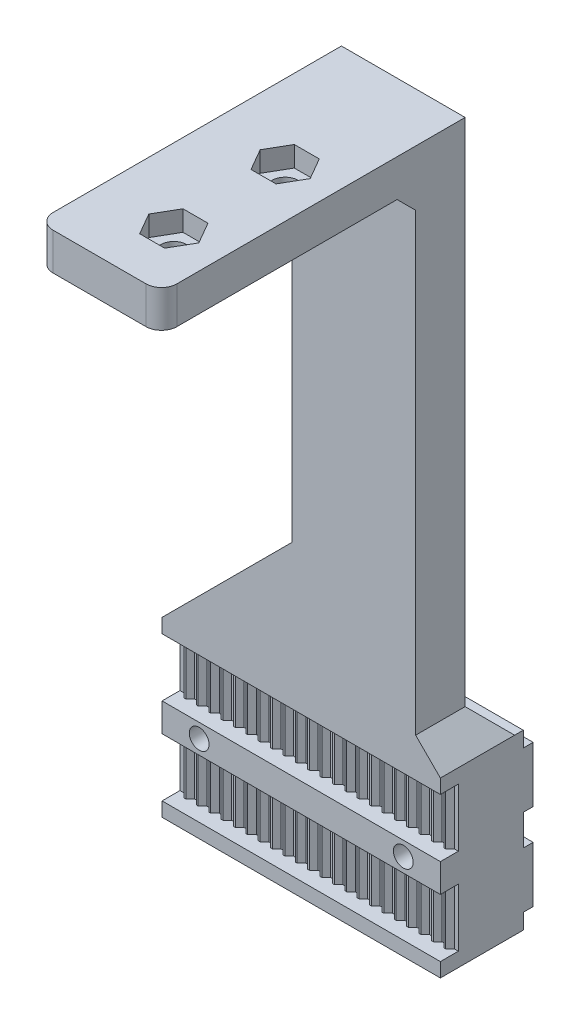
SolidWorks part; units mm, degrees
ref_plane "Спереди" through (0, 0, 0) normal (0, 0, 1) x (1, 0, 0)
ref_plane "Сверху" through (0, 0, 0) normal (0, 1, 0) x (1, 0, 0)
ref_plane "Справа" through (0, 0, 0) normal (1, 0, 0) x (0, 0, -1)
sketch "Эскиз1" plane through (0, 0, 0) normal (0, 0, 1) x (1, 0, 0)
  line L1 (0, -28) -> (-45, -28)
  line L2 (0, -28) -> (0, 0)
  line L3 (0, 0) -> (-45, 0)
  line L4 (-45, -28) -> (-45, 0)
  dimension "D1" = 28
  dimension "D2" = 45
extrude "Бобышка-Вытянуть1" add sketch "Эскиз1" along normal blind 13.4
sketch "Эскиз2" plane through (0, 0, 0) normal (0, 1, 0) x (1, 0, 0)
  line L6 (-45, 0) -> (-45, 1.6)
  line L90 (0, 0) -> (0, 1.6)
  line L91 (0, 0) -> (-45, 0)
  line L93 (-45, 1.6) -> (0, 1.6)
  dimension "D5" = 1.6
extrude "Бобышка-Вытянуть2" add sketch "Эскиз2" against normal blind 9 from offset 2.5 offset against normal yes
extrude "Бобышка-Вытянуть3" add sketch "Эскиз2<2>" against normal blind 9 from offset 16.5 offset against normal yes
sketch "Эскиз2<2>" plane through (0, 0, 0) normal (0, 1, 0) x (1, 0, 0) same geometry as "Эскиз2"
sketch "Эскиз3" plane through (0, 0, 13.4) normal (0, 0, 1) x (1, 0, 0)
  line L1 (-45, -2.3) -> (0, -2.3)
  line L2 (-45, -2.3) -> (-45, -11.7)
  line L3 (-45, -11.7) -> (0, -11.7)
  line L4 (0, -2.3) -> (0, -11.7)
  line L6 (-45, 0) -> (-45, -28) construction
  line L7 (0, -28) -> (0, 0) construction
  line L8 (0, 0) -> (-45, 0) construction
  line L9 (-45, -16.3) -> (0, -16.3)
  line L10 (-45, -16.3) -> (-45, -25.7)
  line L11 (-45, -25.7) -> (0, -25.7)
  line L12 (0, -16.3) -> (0, -25.7)
  line L13 (-45, -28) -> (0, -28) construction
  dimension "D1" = 9.4
  dimension "D2" = 45
  dimension "D3" = 9.4
  dimension "D4" = 45
  dimension "D5" = 4.6
  dimension "D6" = 2.3
  dimension "D7" = 2.3
extrude "Вырез-Вытянуть1" cut sketch "Эскиз3" against normal blind 2.9
sketch "Эскиз4" plane through (0, 0, 13.4) normal (0, 0, 1) x (1, 0, 0)
  line L0 (-45, -11.7) -> (-45, -16.3) construction
  line L1 (0, -16.3) -> (0, -11.7) construction
  circle A0 centre (-39, -14) radius 1.6
  circle A1 centre (-6, -14) radius 1.6
  point P9 (-45, -14)
  dimension "D1" = 3.2
  dimension "D2" = 3.2
  dimension "D4" = 6
  dimension "D3" = 6
extrude "Вырез-Вытянуть2" cut sketch "Эскиз4" against normal through all
sketch "Эскиз5" plane through (0, -2.3, 0) normal (0, -1, 0) x (1, 0, 0)
  line L0 (-45, 10.5) -> (-44.35, 10.5)
  line L1 (0, 10.5) -> (-45, 10.5) construction
  line L2 (-44.35, 10.5) -> (-43.65, 11.2)
  line L3 (-43.65, 11.2) -> (-43.35, 11.2)
  line L4 (-43.35, 11.2) -> (-42.65, 10.5)
  line L5 (-42.65, 10.5) -> (-42.35, 10.5)
  line L6 (-45, 10.5) -> (-45, 9.5)
  line L7 (-42.35, 10.5) -> (-41.65, 11.2)
  line L8 (-41.65, 11.2) -> (-41.35, 11.2)
  line L9 (-41.35, 11.2) -> (-40.65, 10.5)
  line L10 (-40.65, 10.5) -> (-40.35, 10.5)
  line L11 (-40.35, 10.5) -> (-39.65, 11.2)
  line L12 (-39.65, 11.2) -> (-39.35, 11.2)
  line L13 (-39.35, 11.2) -> (-38.65, 10.5)
  line L14 (-38.65, 10.5) -> (-38.35, 10.5)
  line L15 (-38.35, 10.5) -> (-37.65, 11.2)
  line L16 (-37.65, 11.2) -> (-37.35, 11.2)
  line L17 (-37.35, 11.2) -> (-36.65, 10.5)
  line L18 (-36.65, 10.5) -> (-36.35, 10.5)
  line L19 (-36.35, 10.5) -> (-35.65, 11.2)
  line L20 (-35.65, 11.2) -> (-35.35, 11.2)
  line L21 (-35.35, 11.2) -> (-34.65, 10.5)
  line L22 (-34.65, 10.5) -> (-34.35, 10.5)
  line L23 (-34.35, 10.5) -> (-33.65, 11.2)
  line L24 (-33.65, 11.2) -> (-33.35, 11.2)
  line L25 (-33.35, 11.2) -> (-32.65, 10.5)
  line L26 (-32.65, 10.5) -> (-32.35, 10.5)
  line L27 (-32.35, 10.5) -> (-31.65, 11.2)
  line L28 (-31.65, 11.2) -> (-31.35, 11.2)
  line L29 (-31.35, 11.2) -> (-30.65, 10.5)
  line L30 (-30.65, 10.5) -> (-30.35, 10.5)
  line L31 (-30.35, 10.5) -> (-29.65, 11.2)
  line L32 (-29.65, 11.2) -> (-29.35, 11.2)
  line L33 (-29.35, 11.2) -> (-28.65, 10.5)
  line L34 (-28.65, 10.5) -> (-28.35, 10.5)
  line L35 (-28.35, 10.5) -> (-27.65, 11.2)
  line L36 (-27.65, 11.2) -> (-27.35, 11.2)
  line L37 (-27.35, 11.2) -> (-26.65, 10.5)
  line L38 (-26.65, 10.5) -> (-26.35, 10.5)
  line L39 (-26.35, 10.5) -> (-25.65, 11.2)
  line L40 (-25.65, 11.2) -> (-25.35, 11.2)
  line L41 (-25.35, 11.2) -> (-24.65, 10.5)
  line L42 (-24.65, 10.5) -> (-24.35, 10.5)
  line L43 (-24.35, 10.5) -> (-23.65, 11.2)
  line L44 (-23.65, 11.2) -> (-23.35, 11.2)
  line L45 (-23.35, 11.2) -> (-22.65, 10.5)
  line L46 (-22.65, 10.5) -> (-22.35, 10.5)
  line L47 (-22.35, 10.5) -> (-21.65, 11.2)
  line L48 (-21.65, 11.2) -> (-21.35, 11.2)
  line L49 (-21.35, 11.2) -> (-20.65, 10.5)
  line L50 (-20.65, 10.5) -> (-20.35, 10.5)
  line L51 (-20.35, 10.5) -> (-19.65, 11.2)
  line L52 (-19.65, 11.2) -> (-19.35, 11.2)
  line L53 (-19.35, 11.2) -> (-18.65, 10.5)
  line L54 (-18.65, 10.5) -> (-18.35, 10.5)
  line L55 (-18.35, 10.5) -> (-17.65, 11.2)
  line L56 (-17.65, 11.2) -> (-17.35, 11.2)
  line L57 (-17.35, 11.2) -> (-16.65, 10.5)
  line L58 (-16.65, 10.5) -> (-16.35, 10.5)
  line L59 (-16.35, 10.5) -> (-15.65, 11.2)
  line L60 (-15.65, 11.2) -> (-15.35, 11.2)
  line L61 (-15.35, 11.2) -> (-14.65, 10.5)
  line L62 (-14.65, 10.5) -> (-14.35, 10.5)
  line L63 (-14.35, 10.5) -> (-13.65, 11.2)
  line L64 (-13.65, 11.2) -> (-13.35, 11.2)
  line L65 (-13.35, 11.2) -> (-12.65, 10.5)
  line L66 (-12.65, 10.5) -> (-12.35, 10.5)
  line L67 (-12.35, 10.5) -> (-11.65, 11.2)
  line L68 (-11.65, 11.2) -> (-11.35, 11.2)
  line L69 (-11.35, 11.2) -> (-10.65, 10.5)
  line L70 (-10.65, 10.5) -> (-10.35, 10.5)
  line L71 (-10.35, 10.5) -> (-9.65, 11.2)
  line L72 (-9.65, 11.2) -> (-9.35, 11.2)
  line L73 (-9.35, 11.2) -> (-8.65, 10.5)
  line L74 (-8.65, 10.5) -> (-8.35, 10.5)
  line L75 (-8.35, 10.5) -> (-7.65, 11.2)
  line L76 (-7.65, 11.2) -> (-7.35, 11.2)
  line L77 (-7.35, 11.2) -> (-6.65, 10.5)
  line L78 (-6.65, 10.5) -> (-6.35, 10.5)
  line L79 (-6.35, 10.5) -> (-5.65, 11.2)
  line L80 (-5.65, 11.2) -> (-5.35, 11.2)
  line L81 (-5.35, 11.2) -> (-4.65, 10.5)
  line L82 (-4.65, 10.5) -> (-4.35, 10.5)
  line L83 (-4.35, 10.5) -> (-3.65, 11.2)
  line L84 (-3.65, 11.2) -> (-3.35, 11.2)
  line L85 (-3.35, 11.2) -> (-2.65, 10.5)
  line L86 (-2.65, 10.5) -> (-2.35, 10.5)
  line L87 (-2.35, 10.5) -> (-1.65, 11.2)
  line L88 (-1.65, 11.2) -> (-1.35, 11.2)
  line L89 (-1.35, 11.2) -> (-0.65, 10.5)
  line L90 (-0.65, 10.5) -> (0, 10.5)
  line L91 (-45, 9.5) -> (0, 9.5)
  line L92 (0, 10.5) -> (0, 9.5)
  line L93 (-0.65, 10.5) -> (-0.35, 10.5) [skipped]
  dimension "D1" = 45
  dimension "D2" = 45
  dimension "D3" = 0.7
  dimension "D4" = 2
  dimension "D5" = 0.65
  dimension "D6" = 1
  dimension "D7" = 22
extrude "Бобышка-Вытянуть4" add sketch "Эскиз5" along normal up to surface (9.4 mm away) up to face at (-22.5, -11.7, 11.95)
extrude "Бобышка-Вытянуть5" add sketch "Эскиз5<2>" along normal up to surface (23.4 mm away) from surface up to face at (-22.5, -25.7, 11.95) starting at face at (-22.5, -16.3, 11.95)
sketch "Эскиз5<2>" plane through (0, -2.3, 0) normal (0, -1, 0) x (1, 0, 0) same geometry as "Эскиз5"
sketch "Эскиз17" plane through (0, -13.4, 13.4) normal (0, 0, -1) x (1, 0, 0)
  line L0 (0, -11.1) -> (0, -13.4) construction
  line L6 (-4, -13.4) -> (-45, -13.4)
  line L7 (-4, -13.4) -> (-4, -99.9)
  line L8 (-4, -99.9) -> (-24, -99.9)
  line L9 (-24, -34.4) -> (-24, -99.9)
  line L10 (-45, -13.4) -> (-24, -34.4)
  dimension "D1" = 20
  dimension "D2" = 86.5
  dimension "D3" = 4
  dimension "D4" = 45
extrude "Бобышка-Вытянуть16" add sketch "Эскиз17" along normal blind 8
sketch "Эскиз18" plane through (0, 86.5, 85.9) normal (0, -1, 0) x (1, 0, 0)
  line L1 (-4, -80.5) -> (-24, -80.5)
  line L2 (-4, -80.5) -> (-4, -31.4)
  line L3 (-4, -31.4) -> (-24, -31.4)
  line L4 (-24, -80.5) -> (-24, -31.4)
  line L7 (-24, -80.5) -> (-24, -72.5) construction
  line L10 (-24, -72.5) -> (-4, -72.5) construction
  dimension "D1" = 41.1
extrude "Бобышка-Вытянуть17" add sketch "Эскиз18" along normal blind 6
sketch "Эскиз19" plane through (0, 86.5, 0) normal (0, -1, 0) x (-1, 0, 0)
  line L0 (12, -26.5) -> (12, -44.5) construction
  line L1 (4, -54.5) -> (4, -13.4) construction
  line L2 (24, -54.5) -> (4, -54.5) construction
  circle A0 centre (12, -26.5) radius 2.1
  circle A1 centre (12, -44.5) radius 2.1
  dimension "D1" = 4.2
  dimension "D2" = 4.2
  dimension "D3" = 18
  dimension "D5" = 10
  dimension "D4" = 8
extrude "Вырез-Вытянуть5" cut sketch "Эскиз19" along normal through all
sketch "Эскиз20" plane through (0, 86.5, 0) normal (0, 1, 0) x (-1, 0, 0)
  line L1 (16.0415, 26.5) -> (14.0207, 30)
  line L2 (14.0207, 30) -> (9.9793, 30)
  line L3 (9.9793, 30) -> (7.9585, 26.5)
  line L4 (7.9585, 26.5) -> (9.9793, 23)
  line L5 (9.9793, 23) -> (14.0207, 23)
  line L6 (14.0207, 23) -> (16.0415, 26.5)
  line L7 (16.0415, 44.5) -> (14.0207, 48)
  line L8 (14.0207, 48) -> (9.9793, 48)
  line L9 (9.9793, 48) -> (7.9585, 44.5)
  line L10 (7.9585, 44.5) -> (9.9793, 41)
  line L11 (9.9793, 41) -> (14.0207, 41)
  line L12 (14.0207, 41) -> (16.0415, 44.5)
  circle A0 centre (12, 26.5) radius 3.5 construction
  circle A1 centre (12, 44.5) radius 3.5 construction
  dimension "D1" = 7
extrude "Вырез-Вытянуть6" cut sketch "Эскиз20" against normal blind 3.3
chamfer "Фаска1" distance 4 angle 45 2 edges at (-24.5, 0, 5.4) (-4, 0, 9.4)
chamfer "Фаска2" distance 3 angle 45 1 edges at (-14, 80.5, 13.4)
fillet "Скругление1" radius 2.5 2 edges at (-4, 83.5, 54.5) (-24, 83.5, 54.5)
sketch "Эскиз21" plane through (0, 80.5, 0) normal (0, -1, 0) x (1, 0, 0)
  line L0 (-12, 26.5) -> (-12, 44.5) construction
